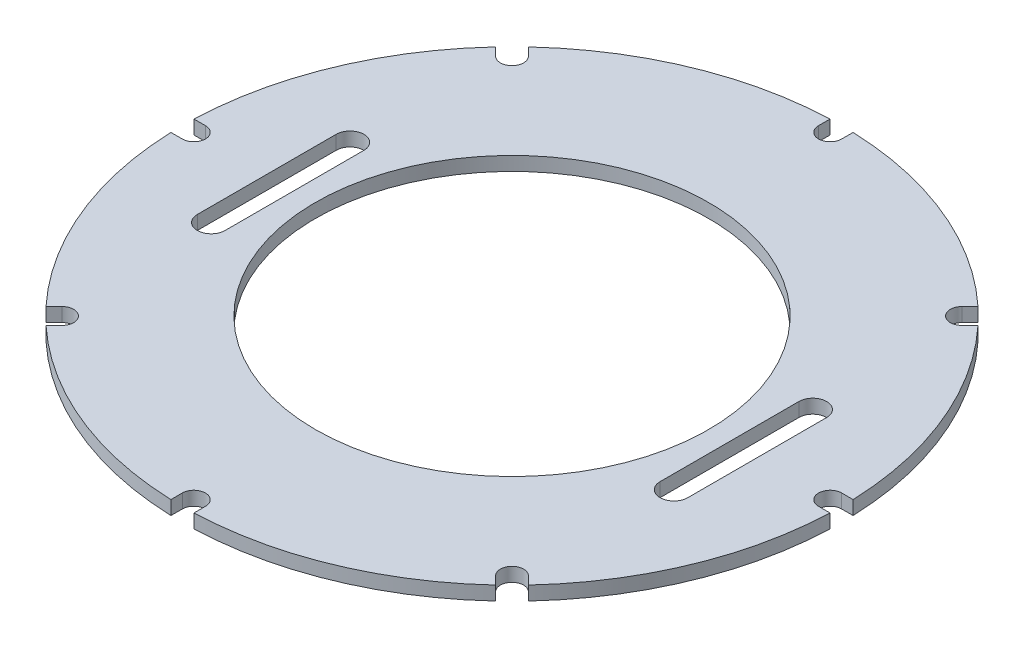
SolidWorks part; units mm, degrees
ref_plane "Front Plane" through (0, 0, 0) normal (0, 0, 1) x (1, 0, 0)
ref_plane "Top Plane" through (0, 0, 0) normal (0, 1, 0) x (1, 0, 0)
ref_plane "Right Plane" through (0, 0, 0) normal (1, 0, 0) x (0, 0, -1)
sketch "Sketch1" plane through (0, 0, 0) normal (0, 1, 0) x (1, 0, 0)
  line L0 (10, -3) -> (10, 3) construction
  line L1 (9.4, -3) -> (9.4, 3)
  line L2 (10.6, -3) -> (10.6, 3)
  line L3 (0, 0) -> (0, -14.25) construction
  line L4 (-10, -3) -> (-10, 3) construction
  line L5 (-9.4, -3) -> (-9.4, 3)
  line L6 (-10.6, -3) -> (-10.6, 3)
  line L7 (-0.5, -13.75) -> (-0.5, -14.2412)
  line L8 (0.5, -13.75) -> (0.5, -14.2412)
  line L9 (-10.0763, -9.3692) -> (-10.4236, -9.7165)
  line L10 (-9.3692, -10.0763) -> (-9.7165, -10.4236)
  line L11 (-13.75, 0.5) -> (-14.2412, 0.5)
  line L12 (-13.75, -0.5) -> (-14.2412, -0.5)
  line L13 (-9.3692, 10.0763) -> (-9.7165, 10.4236)
  line L14 (-10.0763, 9.3692) -> (-10.4236, 9.7165)
  line L15 (0.5, 13.75) -> (0.5, 14.2412)
  line L16 (-0.5, 13.75) -> (-0.5, 14.2412)
  line L17 (10.0763, 9.3692) -> (10.4236, 9.7165)
  line L18 (9.3692, 10.0763) -> (9.7165, 10.4236)
  line L19 (13.75, -0.5) -> (14.2412, -0.5)
  line L20 (13.75, 0.5) -> (14.2412, 0.5)
  line L21 (9.3692, -10.0763) -> (9.7165, -10.4236)
  line L22 (10.0763, -9.3692) -> (10.4236, -9.7165)
  circle A0 centre (0, 0) radius 14.25
  circle A1 centre (0, 0) radius 8.5
  arc A2 (9.4, -3) -> (10.6, -3) centre (10, -3) ccw
  arc A3 (10.6, 3) -> (9.4, 3) centre (10, 3) ccw
  arc A4 (-9.4, -3) -> (-10.6, -3) centre (-10, -3) cw
  arc A5 (-10.6, 3) -> (-9.4, 3) centre (-10, 3) cw
  arc A6 (0.5, -13.75) -> (-0.5, -13.75) centre (0, -13.75) ccw
  arc A7 (-9.3692, -10.0763) -> (-10.0763, -9.3692) centre (-9.7227, -9.7227) ccw
  arc A8 (-13.75, -0.5) -> (-13.75, 0.5) centre (-13.75, 0) ccw
  arc A9 (-10.0763, 9.3692) -> (-9.3692, 10.0763) centre (-9.7227, 9.7227) ccw
  arc A10 (-0.5, 13.75) -> (0.5, 13.75) centre (0, 13.75) ccw
  arc A11 (9.3692, 10.0763) -> (10.0763, 9.3692) centre (9.7227, 9.7227) ccw
  arc A12 (13.75, 0.5) -> (13.75, -0.5) centre (13.75, 0) ccw
  arc A13 (10.0763, -9.3692) -> (9.3692, -10.0763) centre (9.7227, -9.7227) ccw
  point P6 (10, 0)
  point P13 (-10, 0)
  point P61 (0, 0)
  dimension "D1" = 28.5
  dimension "D2" = 17
  dimension "D6" = 8
  dimension "D3" = 1.2
  dimension "D4" = 6
  dimension "D5" = 10
extrude "Boss-Extrude1" add sketch "Sketch1" along normal blind 0.6 contours A13 L22 A0 L19 A12 L20 L17 A11 L18 L15 A10 L16 L13 A9 L14 L11 A8 L12 L9 A7 L10 L7 A6 L8 L21 A3 L2 A2 L1 A1 L6 A5 L5 A4 region at (-0.9028, 0, 13.9956)
